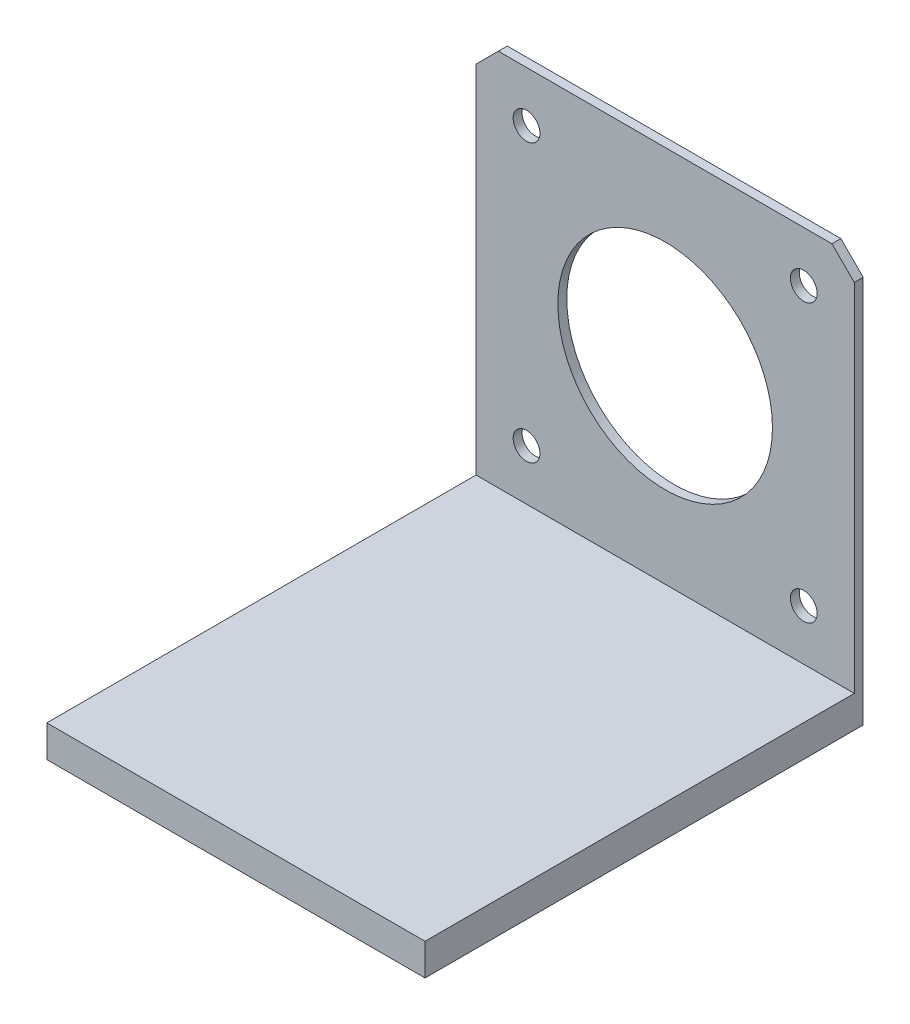
SolidWorks part; units mm, degrees
ref_plane "Alzado" through (0, 0, 0) normal (0, 0, 1) x (1, 0, 0)
ref_plane "Planta" through (0, 0, 0) normal (0, 1, 0) x (1, 0, 0)
ref_plane "Vista lateral" through (0, 0, 0) normal (1, 0, 0) x (0, 0, -1)
sketch "Sketch1" plane through (0, 0, 0) normal (0, 0, 1) x (1, 0, 0)
  line L1 (-25.8145, 17.8273) -> (16.4855, 17.8273)
  line L2 (-25.8145, 17.8273) -> (-25.8145, -24.4727)
  line L3 (-25.8145, -24.4727) -> (16.4855, -24.4727)
  line L4 (16.4855, 17.8273) -> (16.4855, -24.4727)
  dimension "D1" = 42.3
  dimension "D2" = 42.3
extrude "Boss-Extrude1" add sketch "Sketch1" along normal blind 1
sketch "Sketch3" plane through (0, 0, 1) normal (0, 0, 1) x (1, 0, 0)
  line L0 (-25.8145, -24.4727) -> (16.4855, -24.4727) construction
  line L1 (-25.8145, 17.8273) -> (-25.8145, -24.4727) construction
  circle A0 centre (-20.1645, -18.8227) radius 0.5
  circle A1 centre (10.8355, -18.8227) radius 0.5
  circle A2 centre (10.8355, 12.1773) radius 0.5
  circle A3 centre (-20.1645, 12.1773) radius 0.5
  dimension "D1" = 5.65
  dimension "D3" = 31
  dimension "D4" = 31
  dimension "D5" = 31
  dimension "D2" = 5.65
extrude "Cut-Extrude1" cut sketch "Sketch3" against normal through all
chamfer "Chamfer1" distance 2.5 angle 45 4 edges at (-25.8145, -24.4727, 0.5) (16.4855, -24.4727, 0.5) (16.4855, 17.8273, 0.5) (-25.8145, 17.8273, 0.5)
sketch "Sketch4" plane through (0, 0, 1) normal (0, 0, 1) x (1, 0, 0)
  circle A0 centre (-4.6645, -3.3227) radius 12
extrude "Cut-Extrude2" cut sketch "Sketch4" against normal through all
sketch "Sketch5" plane through (0, 0, 1) normal (0, 0, 1) x (1, 0, 0)
  circle A0 centre (-20.1645, 12.1773) radius 1.5
  circle A1 centre (-20.1645, -18.8227) radius 1.5
  circle A2 centre (10.8355, -18.8227) radius 1.5
  circle A3 centre (10.8355, 12.1773) radius 1.5
extrude "Cut-Extrude3" cut sketch "Sketch5" against normal through all
sketch "Sketch6" plane through (0, -24.4727, 0) normal (0, -1, 0) x (1, 0, 0)
  line L1 (-25.8145, 1) -> (16.4855, 1)
  line L2 (-25.8145, 1) -> (-25.8145, 0)
  line L3 (-25.8145, 0) -> (16.4855, 0)
  line L4 (16.4855, 1) -> (16.4855, 0)
extrude "Boss-Extrude2" add sketch "Sketch6" along normal blind 3.21
sketch "Sketch7" plane through (0, 0, 1) normal (0, 0, 1) x (1, 0, 0)
  line L1 (-25.8145, -21.9727) -> (16.4855, -21.9727)
  line L2 (-25.8145, -21.9727) -> (-25.8145, -27.6827)
  line L3 (-25.8145, -27.6827) -> (16.4855, -27.6827)
  line L4 (16.4855, -21.9727) -> (16.4855, -27.6827)
extrude "Boss-Extrude3" add sketch "Sketch7" against normal blind 1
sketch "Sketch8" plane through (0, -27.6827, 0) normal (0, -1, 0) x (1, 0, 0)
  line L1 (-25.8145, 1) -> (16.4855, 1)
  line L2 (-25.8145, 1) -> (-25.8145, 0)
  line L3 (-25.8145, 0) -> (16.4855, 0)
  line L4 (16.4855, 1) -> (16.4855, 0)
extrude "Boss-Extrude4" add sketch "Sketch8" along normal blind 0.35
sketch "Sketch9" plane through (0, 0, 1) normal (0, 0, 1) x (1, 0, 0)
  line L5 (-25.8145, -28.0327) -> (-25.8145, -25.4727) construction
  line L6 (-25.8145, 15.3273) -> (-25.8145, -28.0327) construction
  line L7 (16.4855, -28.0327) -> (16.4855, 15.3273) construction
  line L8 (-25.8145, -25.4727) -> (16.4855, -25.4727)
  line L9 (-25.8145, -25.4727) -> (-25.8145, -24.4727)
  line L10 (-25.8145, -24.4727) -> (16.4855, -24.4727)
  line L11 (16.4855, -25.4727) -> (16.4855, -24.4727)
  dimension "D1" = 2.56
  dimension "D2" = 1
extrude "Boss-Extrude5" add sketch "Sketch9" along normal blind 48
sketch "Sketch10" plane through (0, -25.4727, 0) normal (0, -1, 0) x (1, 0, 0)
  line L0 (16.4855, 49) -> (16.4855, 1) construction
  line L1 (-25.8145, 49) -> (16.4855, 49)
  line L2 (-25.8145, 49) -> (-25.8145, 48)
  line L3 (-25.8145, 48) -> (16.4855, 48)
  line L4 (16.4855, 49) -> (16.4855, 48)
  dimension "D1" = 1
extrude "Boss-Extrude6" add sketch "Sketch10" along normal blind 2.56
sketch "Sketch11" plane through (-25.8145, 0, 0) normal (-1, 0, 0) x (0, 0, 1)
  line L1 (0, -28.0327) -> (49, -28.0327)
  line L2 (0, -28.0327) -> (0, -24.4727)
  line L3 (0, -24.4727) -> (49, -24.4727)
  line L4 (49, -28.0327) -> (49, -24.4727)
extrude "Boss-Extrude7" add sketch "Sketch11" against normal blind 1
sketch "Sketch12" plane through (-25.8145, 0, 0) normal (-1, 0, 0) x (0, 0, 1)
  line L0 (49, -28.0327) -> (0, -28.0327) construction
  line L1 (22, -28.0327) -> (27, -28.0327)
  line L2 (22, -28.0327) -> (22, -27.0327)
  line L3 (22, -27.0327) -> (27, -27.0327)
  line L4 (27, -28.0327) -> (27, -27.0327)
  dimension "D1" = 1
  dimension "D2" = 5
  dimension "D3" = 22
extrude "Boss-Extrude8" add sketch "Sketch12" along normal blind 5
sketch "Sketch13" plane through (16.4855, 0, 0) normal (1, 0, 0) x (0, 0, -1)
  line L1 (-49, -24.4727) -> (0, -24.4727)
  line L2 (-49, -24.4727) -> (-49, -28.0327)
  line L3 (-49, -28.0327) -> (0, -28.0327)
  line L4 (0, -24.4727) -> (0, -28.0327)
extrude "Boss-Extrude9" add sketch "Sketch13" against normal blind 1
sketch "Sketch14" plane through (0, -24.4727, 0) normal (0, 1, 0) x (1, 0, 0)
  line L0 (-25.8145, -27) -> (16.4855, -27) construction
  line L1 (16.4855, -49) -> (16.4855, -1) construction
  line L3 (16.4855, -27) -> (21.4855, -27)
  line L4 (16.4855, -27) -> (16.4855, -22)
  line L5 (16.4855, -22) -> (21.4855, -22)
  line L6 (21.4855, -27) -> (21.4855, -22)
  dimension "D1" = 5
  dimension "D2" = 5
extrude "Boss-Extrude10" add sketch "Sketch14" against normal up to vertex (3.56 mm away) up to point (-30.8145, -28.0327, 27)
sketch "Sketch15" plane through (21.4855, 0, 0) normal (1, 0, 0) x (0, 0, -1)
  line L0 (-27, -28.0327) -> (-27, -24.4727) construction
  line L1 (-22, -24.4727) -> (-27, -24.4727)
  line L2 (-22, -24.4727) -> (-22, -27.0327)
  line L3 (-22, -27.0327) -> (-27, -27.0327)
  line L4 (-27, -24.4727) -> (-27, -27.0327)
  dimension "D1" = 1
extrude "Cut-Extrude4" cut sketch "Sketch15" against normal blind 5
sketch "Sketch16" plane through (0, -27.0327, 0) normal (0, 1, 0) x (1, 0, 0)
  circle A0 centre (-28.3145, -24.5) radius 1
  circle A1 centre (18.9855, -24.5) radius 1
extrude "Cut-Extrude5" cut sketch "Sketch16" against normal blind 5
sketch "Sketch17" plane through (0, -27.0327, 0) normal (0, 1, 0) x (1, 0, 0)
  line L1 (-30.8145, -27) -> (-25.8145, -27)
  line L2 (-30.8145, -27) -> (-30.8145, -22)
  line L3 (-30.8145, -22) -> (-25.8145, -22)
  line L4 (-25.8145, -27) -> (-25.8145, -22)
  circle A0 centre (-28.3145, -24.5) radius 1
extrude "Boss-Extrude11" add sketch "Sketch17" along normal up to vertex (2.56 mm away) up to point (-25.8145, -24.4727, 49)
sketch "Sketch19" plane through (0, -24.4727, 0) normal (0, 1, 0) x (1, 0, 0)
  line L1 (-29.4692, -26.5) -> (-27.1598, -26.5)
  line L2 (-27.1598, -26.5) -> (-26.0051, -24.5)
  line L3 (-26.0051, -24.5) -> (-27.1598, -22.5)
  line L4 (-27.1598, -22.5) -> (-29.4692, -22.5)
  line L5 (-29.4692, -22.5) -> (-30.6239, -24.5)
  line L6 (-30.6239, -24.5) -> (-29.4692, -26.5)
  circle A0 centre (-28.3145, -24.5) radius 2 construction
extrude "Cut-Extrude6" cut sketch "Sketch19" against normal blind 5
sketch "Sketch20" plane through (-30.8145, 0, 0) normal (-1, 0, 0) x (0, 0, 1)
  line L1 (27, -24.4727) -> (22, -24.4727)
  line L2 (27, -24.4727) -> (27, -28.0327)
  line L3 (27, -28.0327) -> (22, -28.0327)
  line L4 (22, -24.4727) -> (22, -28.0327)
extrude "Boss-Extrude12" add sketch "Sketch20" along normal blind 1
sketch "Sketch21" plane through (0, 0, 27) normal (0, 0, 1) x (1, 0, 0)
  line L1 (-25.8145, -24.4727) -> (-31.8145, -24.4727)
  line L2 (-25.8145, -24.4727) -> (-25.8145, -28.0327)
  line L3 (-25.8145, -28.0327) -> (-31.8145, -28.0327)
  line L4 (-31.8145, -24.4727) -> (-31.8145, -28.0327)
extrude "Boss-Extrude13" add sketch "Sketch21" along normal blind 1
sketch "Sketch22" plane through (0, 0, 22) normal (0, 0, -1) x (-1, 0, 0)
  line L1 (31.8145, -24.4727) -> (25.8145, -24.4727)
  line L2 (31.8145, -24.4727) -> (31.8145, -28.0327)
  line L3 (31.8145, -28.0327) -> (25.8145, -28.0327)
  line L4 (25.8145, -24.4727) -> (25.8145, -28.0327)
extrude "Boss-Extrude14" add sketch "Sketch22" along normal blind 1
sketch "Sketch23" plane through (0, -27.0327, 0) normal (0, 1, 0) x (1, 0, 0)
  line L1 (21.4855, -27) -> (16.4855, -27)
  line L2 (21.4855, -27) -> (21.4855, -22)
  line L3 (21.4855, -22) -> (16.4855, -22)
  line L4 (16.4855, -27) -> (16.4855, -22)
extrude "Boss-Extrude15" add sketch "Sketch23" along normal up to vertex (2.56 mm away) up to point (16.4855, -24.4727, 49)
sketch "Sketch24" plane through (0, 0, 27) normal (0, 0, 1) x (1, 0, 0)
  line L1 (21.4855, -24.4727) -> (16.4855, -24.4727)
  line L2 (21.4855, -24.4727) -> (21.4855, -28.0327)
  line L3 (21.4855, -28.0327) -> (16.4855, -28.0327)
  line L4 (16.4855, -24.4727) -> (16.4855, -28.0327)
extrude "Boss-Extrude16" add sketch "Sketch24" along normal blind 1
sketch "Sketch25" plane through (0, 0, 22) normal (0, 0, -1) x (-1, 0, 0)
  line L1 (-21.4855, -24.4727) -> (-16.4855, -24.4727)
  line L2 (-21.4855, -24.4727) -> (-21.4855, -28.0327)
  line L3 (-21.4855, -28.0327) -> (-16.4855, -28.0327)
  line L4 (-16.4855, -24.4727) -> (-16.4855, -28.0327)
extrude "Boss-Extrude17" add sketch "Sketch25" along normal blind 1
sketch "Sketch26" plane through (21.4855, 0, 0) normal (1, 0, 0) x (0, 0, -1)
  line L1 (-28, -24.4727) -> (-21, -24.4727)
  line L2 (-28, -24.4727) -> (-28, -28.0327)
  line L3 (-28, -28.0327) -> (-21, -28.0327)
  line L4 (-21, -24.4727) -> (-21, -28.0327)
extrude "Boss-Extrude18" add sketch "Sketch26" along normal blind 1
sketch "Sketch29" plane through (0, -24.4727, 0) normal (0, 1, 0) x (1, 0, 0)
  line L0 (22.4855, -24.5) -> (19.4855, -24.5) construction
  line L1 (22.4855, -21) -> (22.4855, -28) construction
  line L3 (20.6402, -26.5) -> (21.7949, -24.5)
  line L4 (21.7949, -24.5) -> (20.6402, -22.5)
  line L5 (20.6402, -22.5) -> (18.3308, -22.5)
  line L6 (18.3308, -22.5) -> (17.1761, -24.5)
  line L7 (17.1761, -24.5) -> (18.3308, -26.5)
  line L8 (18.3308, -26.5) -> (20.6402, -26.5)
  circle A0 centre (19.4855, -24.5) radius 2 construction
extrude "Cut-Extrude7" cut sketch "Sketch29" against normal blind 21
sketch "Sketch31" plane through (0, -24.4727, 0) normal (0, 1, 0) x (1, 0, 0)
  line L1 (22.4855, -21) -> (16.4855, -21)
  line L2 (22.4855, -21) -> (22.4855, -28)
  line L3 (22.4855, -28) -> (16.4855, -28)
  line L4 (16.4855, -21) -> (16.4855, -28)
extrude "Cut-Extrude8" cut sketch "Sketch31" against normal through all
sketch "Sketch32" plane through (0, -25.4727, 0) normal (0, -1, 0) x (1, 0, 0)
  line L0 (-24.8145, 1) -> (-24.8145, 48) construction
  line L1 (-24.8145, 28) -> (-18.8145, 28)
  line L2 (-24.8145, 28) -> (-24.8145, 21)
  line L3 (-24.8145, 21) -> (-18.8145, 21)
  line L4 (-18.8145, 28) -> (-18.8145, 21)
  dimension "D1" = 6
extrude "Boss-Extrude19" add sketch "Sketch32" along normal up to vertex (2.56 mm away) up to point (-24.8145, -28.0327, 1)
sketch "Sketch34" plane through (0, -28.0327, 0) normal (0, -1, 0) x (-1, 0, 0)
  line L0 (18.8145, -28) -> (-15.4855, -28) construction
  line L1 (-15.4855, -48) -> (-15.4855, -1) construction
  line L3 (-15.4855, -28) -> (-9.4855, -28)
  line L4 (-15.4855, -28) -> (-15.4855, -21)
  line L5 (-15.4855, -21) -> (-9.4855, -21)
  line L6 (-9.4855, -28) -> (-9.4855, -21)
  dimension "D1" = 6
extrude "Boss-Extrude20" add sketch "Sketch34" against normal up to vertex (2.56 mm away) up to point (15.4855, -25.4727, 48)
sketch "Sketch35" plane through (0, -28.0327, 0) normal (0, -1, 0) x (1, 0, 0)
  line L1 (-25.8145, 28) -> (-31.8145, 28)
  line L2 (-25.8145, 28) -> (-25.8145, 21)
  line L3 (-25.8145, 21) -> (-31.8145, 21)
  line L4 (-31.8145, 28) -> (-31.8145, 21)
extrude "Cut-Extrude9" cut sketch "Sketch35" against normal through all
